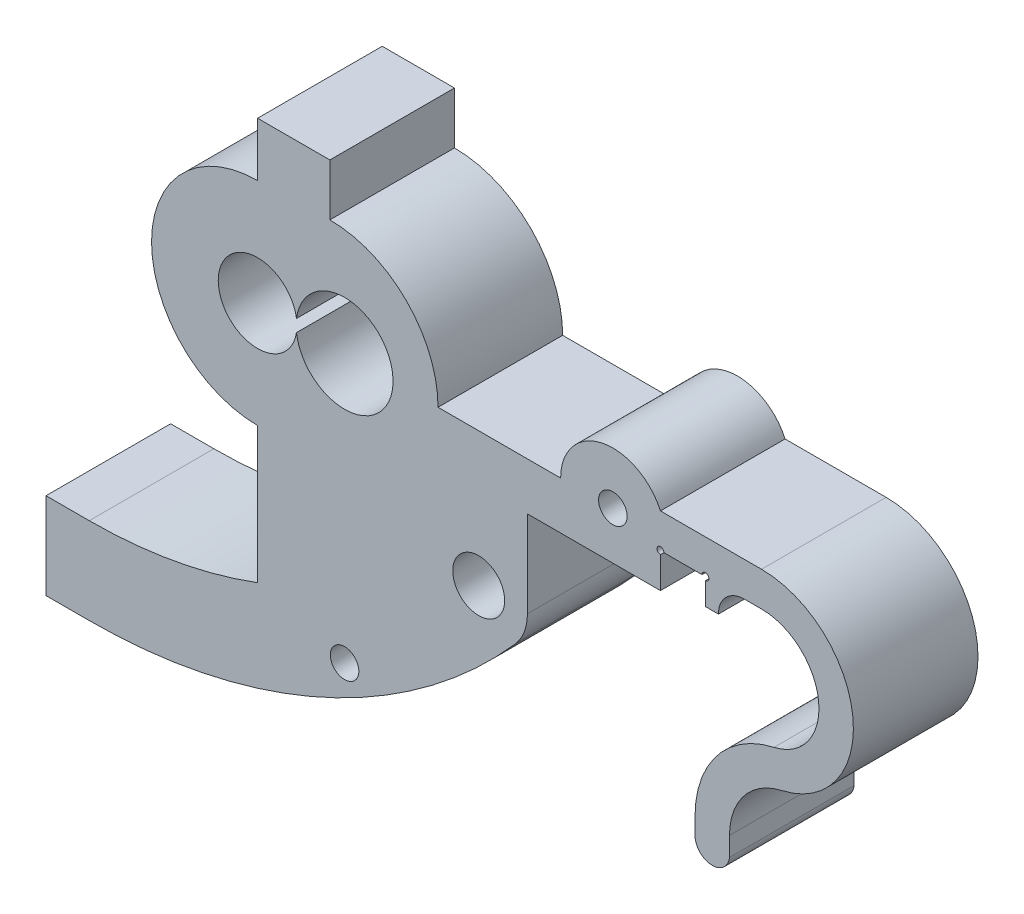
SolidWorks part; units mm, degrees
material "Custom Plastic"
ref_plane "Front Plane" through (0, 0, 0) normal (0, 0, 1) x (1, 0, 0)
ref_plane "Top Plane" through (0, 0, 0) normal (0, 1, 0) x (1, 0, 0)
ref_plane "Right Plane" through (0, 0, 0) normal (1, 0, 0) x (0, 0, -1)
sketch "Sketch1" plane through (0, 0, 0) normal (0, 0, 1) x (1, 0, 0)
  line L0 (-21, -21) -> (21, -21) construction
  line L1 (-21, -21) -> (-21, 21) construction
  line L2 (21, -21) -> (21, 21) construction
  line L3 (-21, 21) -> (21, 21) construction
  line L4 (-21, -21) -> (21, 21) construction
  line L5 (21, -21) -> (-21, 21) construction
  line L6 (25.6769, 16.0403) -> (32.6769, 16.0403) construction
  line L7 (15.5, -15.5) -> (15.5, 15.5) construction
  line L8 (15.5, 15.5) -> (-15.5, 15.5) construction
  line L9 (-15.5, 15.5) -> (-15.5, -15.5) construction
  line L10 (-15.5, -15.5) -> (15.5, -15.5) construction
  line L11 (-50, -26) -> (-45, -26)
  line L12 (-50, -26) -> (-50, -16)
  line L13 (-50, -16) -> (-45, -16)
  line L14 (4.2293, -3.7139) -> (-45, 39.5162) construction
  line L15 (21.4, 14) -> (25.8, 14)
  line L16 (26.2, 13.6) -> (26.2, 11)
  line L17 (-4.7, 15.5) -> (9.4677, 15.5)
  line L18 (25.6769, 14) -> (32.6769, 14) construction
  line L19 (-17.2, 34) -> (-17.2, 28)
  line L20 (5.6286, 10) -> (5.6286, 0)
  line L21 (21, 10) -> (21, 13.6)
  line L22 (5.6286, 10) -> (21, 10)
  line L23 (25.6769, 17.9775) -> (32.6769, 17.9775) construction
  line L24 (32.6769, 17.9775) -> (21, 17.9775)
  line L25 (-25.55, 34) -> (-17.2, 34)
  line L26 (-25.55, 3.2457) -> (-25.55, -12.4814)
  line L27 (-25.55, 27.7543) -> (-25.55, 34)
  line L28 (26.2, 11) -> (27.7, 11)
  line L29 (30.7, 14) -> (32.6769, 14)
  line L32 (25, -10.5) -> (25, -12.7114)
  line L34 (28.9775, -10.5) -> (28.9775, -12.7108)
  circle A0 centre (0, 0) radius 11 construction
  circle A1 centre (0, 0) radius 15.5 construction
  circle A2 centre (0, 0) radius 3
  circle A3 centre (-15.5, 15.5) radius 1.65
  circle A4 centre (15.5, 15.5) radius 1.65
  circle A5 centre (15.5, -15.5) radius 1.65 construction
  circle A6 centre (-15.5, -15.5) radius 1.65
  arc A7 (32.6769, 16.0403) -> (34.5662, -1.1109) centre (32.6769, 7.3606) cw construction
  arc A8 (34.5662, -1.1109) -> (27.0403, -10.5) centre (36.66, -10.5) ccw construction
  arc A9 (32.6769, 14) -> (34.1221, 0.8805) centre (32.6769, 7.3606) cw
  arc A10 (34.1221, 0.8805) -> (25, -10.5) centre (36.66, -10.5) ccw
  arc A11 (32.6769, 17.9775) -> (34.9878, -3.0017) centre (32.6769, 7.3606) cw
  arc A12 (34.9878, -3.0017) -> (28.9775, -10.5) centre (36.66, -10.5) ccw
  arc A14 (4.2293, -3.7139) -> (5.6286, 0) centre (0, 0) ccw
  arc A15 (-25.55, 27.7543) -> (-25.55, 3.2457) centre (-25.55, 15.5) ccw
  arc A16 (-45, -16) -> (-25.55, -12.4814) centre (-45, 39.5162) ccw
  arc A17 (21, 17.9775) -> (9.4677, 15.5) centre (15.5, 15.5) ccw
  arc A18 (-45, -26) -> (4.2293, -3.7139) centre (-45, 39.5162) ccw
  arc A19 (30.7, 14) -> (27.7, 11) centre (30.7, 11) ccw
  arc A20 (-4.7, 15.5) -> (-17.2, 28) centre (-17.2, 15.5) ccw
  arc A21 (26.2, 13.6) -> (25.8, 14) centre (26.2, 14) ccw
  arc A22 (21.4, 14) -> (21, 13.6) centre (21, 14) ccw
  arc A23 (25, -12.7114) -> (28.9775, -12.7108) centre (26.9887, -12.4993) ccw
  dimension "D2" = 22
  dimension "D3" = 31
  dimension "D4" = 3.3
  dimension "D5" = 6
  dimension "D20" = 0.8
  dimension "D16" = 2
  dimension "D1" = 42
  dimension "D10" = 7
  dimension "D6" = 24.5
  dimension "D8" = 50
  dimension "D11" = 26
  dimension "D12" = 5
  dimension "D9" = 14
  dimension "D13" = 17.2
  dimension "D14" = 10
  dimension "D15" = 10.05
  dimension "D7" = 4
  dimension "D17" = 1.5
  dimension "D18" = 3
  dimension "D19" = 5.2
  dimension "D21" = 2
extrude "Boss-Extrude1" add sketch "Sketch1" along normal blind 14.4
sketch "Sketch2" plane through (0, 0, 14.4) normal (0, 0, 1) x (1, 0, 0)
  line L0 (-15.5, 15.5) -> (-25.55, 15.5) construction
  line L1 (-22.25, 26.964) -> (-20.5, 26.964) construction
  line L2 (-22.25, 26.964) -> (-22.25, 3.6636) construction
  line L3 (-22.25, 3.6636) -> (-20.5, 3.6636) construction
  line L4 (-20.5, 26.964) -> (-20.5, 3.6636) construction
  circle A0 centre (-25.55, 15.5) radius 3.8 construction
  circle A1 centre (-15.5, 15.5) radius 5 construction
  circle A2 centre (-25.55, 15.5) radius 4.55
  circle A3 centre (0, 0) radius 11 construction
  circle A4 centre (-15.5, 15.5) radius 1.65 construction
  point P11 (-21.75, 15.5)
  dimension "D3" = 7.6
  dimension "D4" = 9.1
  dimension "D5" = 10
  dimension "D6" = 22
  dimension "D1" = 1.75
  dimension "D2" = 0.5
extrude "Cut-Extrude1" cut sketch "Sketch2" against normal through all
sketch "Sketch3" plane through (0, 0, 14.4) normal (0, 0, 1) x (1, 0, 0)
  circle A0 centre (-15.5, 15.5) radius 5.6
  circle A1 centre (-15.5, 15.5) radius 1.65 construction
  dimension "D1" = 11.2
extrude "Cut-Extrude2" cut sketch "Sketch3" against normal blind 9.5
equation "\"D1@Sketch19\"=1.9/2"
equation "\"y-plate-thickness\"=5"
equation "\"bed-plate-thickness\"=6"
equation "\"x-plate-thickness\"=5"
equation "\"D7@Sketch1\"=\"x-plate-thickness\"-1"
equation "\"y-cross-rib-thickness\"=6"
equation "\"y-rib-thickness\"=6"
equation "\"rod-diameter\"=12"
equation "\"t-nut-hole-diameter\"=3"
equation "\"enclosure-thickness\"=0.6"
equation "\"M3-Clearance\"=3.3"
equation "\"M4-Clearance\"=4.3"
equation "\"M5-Clearance\"=5.3"
equation "\"M6-Clearance\"=6.3"
equation "\"M8-Clearance\"=8.3"
equation "\"623-Bearing-Dia\"=11.2"
